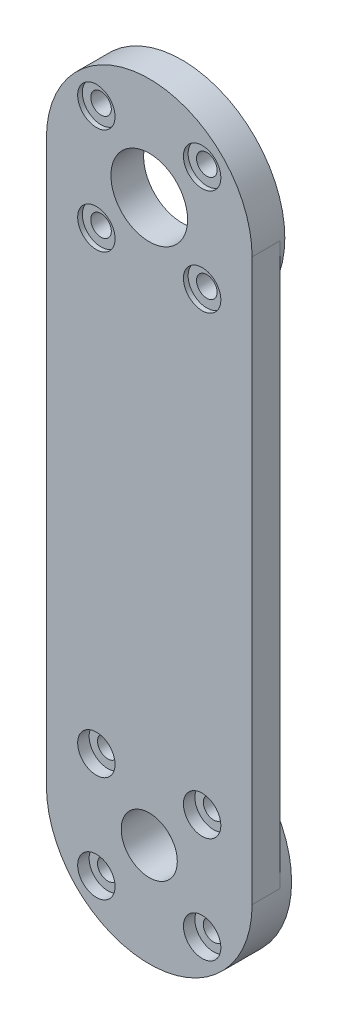
SolidWorks part; units mm, degrees
ref_plane "Front Plane" through (0, 0, 0) normal (0, 0, 1) x (1, 0, 0)
ref_plane "Top Plane" through (0, 0, 0) normal (0, 1, 0) x (1, 0, 0)
ref_plane "Right Plane" through (0, 0, 0) normal (1, 0, 0) x (0, 0, -1)
sketch "Sketch1" plane through (0, 0, 0) normal (0, 0, 1) x (1, 0, 0)
  line L0 (0, 30) -> (0, -30) construction
  line L2 (11, 30) -> (11, -30)
  line L4 (-11, 30) -> (-11, -30)
  circle A0 centre (0, 30) radius 11
  circle A1 centre (0, -30) radius 11
  point P0 (0, 0)
  point P2 (0, 0)
  dimension "D3" = 22
  dimension "D1" = 60
  dimension "D2" = 22
extrude "Boss-Extrude1" add sketch "Sketch1" along normal blind 3 contours A1 L2 A0 L4 | A0 | A1 | A0 L0 A1 L2 region at (5.8363, 0, 0) region at (-5.8363, 0, 0) region at (-7.5582, 22.4418, 0) region at (7.5582, -22.4418, 0)
extrude "Boss-Extrude2" add sketch "Sketch1<3>" against normal blind 0.5 contours A0 region at (0, 30, 0)
sketch "Sketch1<3>" plane through (0, 0, 0) normal (0, 0, 1) x (1, 0, 0) same geometry as "Sketch1"
sketch "Sketch2" plane through (0, 0, 3) normal (0, 0, 1) x (1, 0, 0)
  line L0 (0, 30) -> (5.6569, 35.6569) construction
  line L1 (11, 30) -> (11, -30) construction
  circle A0 centre (0, 30) radius 4.1
  circle A1 centre (5.6569, 35.6569) radius 1.1
  circle A2 centre (5.6569, 35.6569) radius 2
  dimension "D1" = 8.2
  dimension "D2" = 2.2
  dimension "D5" = 4
  dimension "D3" = 8
  dimension "D4" = 45
extrude "Cut-Extrude1" cut sketch "Sketch2" against normal up to surface (3.5 mm away) contours A0 | A1 region at (0, 30, 3) region at (5.6569, 35.6569, 3) up to face at (11, 30, -0.5)
extrude "Cut-Extrude2" cut sketch "Sketch2<3>" against normal offset from surface (0.5 mm away) 3 contours A2 A1 region at (3.7134, 35.6569, 3) up to face at (4.1, 30, -0.5)
sketch "Sketch2<3>" plane through (0, 0, 3) normal (0, 0, 1) x (1, 0, 0) same geometry as "Sketch2"
pattern_circular "CirPattern2" count 4 over 360 about axis through (0, 30, 3) along (0, 0, 1) of "Cut-Extrude2", "Cut-Extrude1"
extrude "Boss-Extrude3" add sketch "Sketch1<5>" against normal blind 1.225 contours A1 region at (0, -30, 0)
sketch "Sketch1<5>" plane through (0, 0, 0) normal (0, 0, 1) x (1, 0, 0) same geometry as "Sketch1"
sketch "Sketch3" plane through (0, 0, 3) normal (0, 0, 1) x (1, 0, 0)
  line L0 (5.6569, -24.3431) -> (0, -30) construction
  line L1 (11, 30) -> (11, -30) construction
  circle A0 centre (0, -30) radius 3
  circle A1 centre (5.6569, -24.3431) radius 1.1
  circle A2 centre (5.6569, -24.3431) radius 2
  dimension "D2" = 6
  dimension "D3" = 2.2
  dimension "D5" = 4
  dimension "D1" = 45
  dimension "D4" = 8
extrude "Cut-Extrude3" cut sketch "Sketch3" against normal up to surface (4.225 mm away) contours A0 | A1 region at (0, -30, 3) up to face at (11, -30, -1.225)
extrude "Cut-Extrude4" cut sketch "Sketch3<3>" against normal offset from surface (1.225 mm away) 3 contours A1 A2 region at (3.7134, -24.3431, 3) up to face at (3, -30, -1.225)
sketch "Sketch3<3>" plane through (0, 0, 3) normal (0, 0, 1) x (1, 0, 0) same geometry as "Sketch3"
pattern_circular "CirPattern3" count 4 over 360 about axis through (0, -30, 3) along (0, 0, 1) of "Cut-Extrude4", "Cut-Extrude3"
